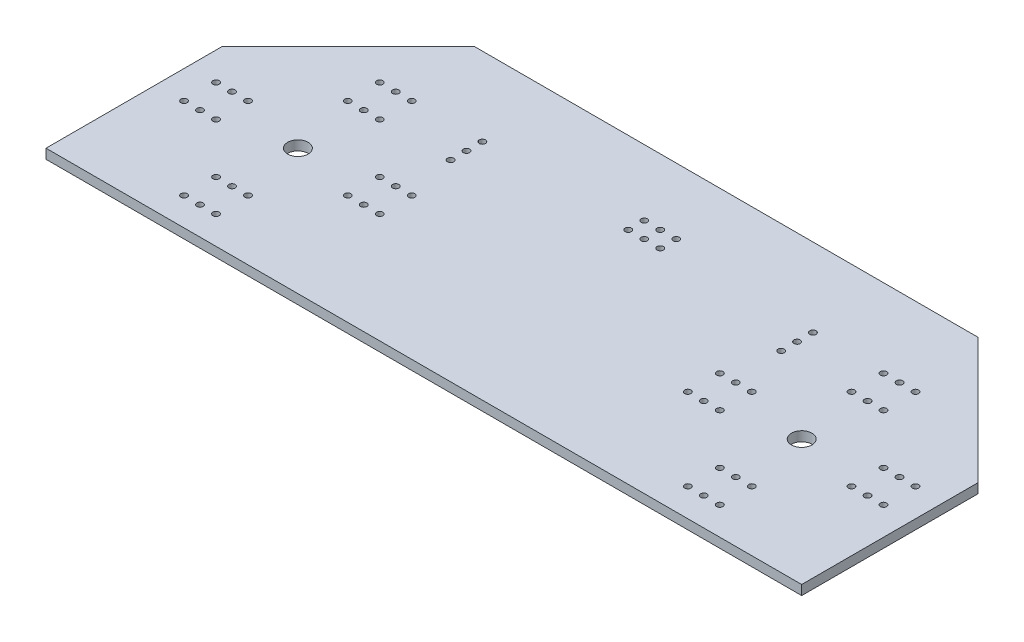
SolidWorks part; units mm, degrees
ref_plane "Front Plane" through (0, 0, 0) normal (0, 0, 1) x (1, 0, 0)
ref_plane "Top Plane" through (0, 0, 0) normal (0, 1, 0) x (1, 0, 0)
ref_plane "Right Plane" through (0, 0, 0) normal (1, 0, 0) x (0, 0, -1)
sketch "Sketch1" plane through (0, 0, 0) normal (0, 1, 0) x (1, 0, 0)
  line L0 (0, 0) -> (0, 13) construction
  line L1 (-60, -20) -> (60, -20)
  line L2 (-60, -20) -> (-60, 28)
  line L3 (-60, 28) -> (60, 28)
  line L4 (60, -20) -> (60, 28)
  line L5 (0, 0) -> (60, 28) construction
  line L6 (-60, 28) -> (0, 0) construction
  line L11 (0, 13) -> (0, 28) construction
  point P0 (0, 0)
  dimension "D1" = 120
  dimension "D2" = 28
  dimension "D6" = 20
extrude "Boss-Extrude1" add sketch "Sketch1" along normal blind 1.53
sketch "Sketch2" plane through (0, 1.53, 0) normal (0, 1, 0) x (1, 0, 0)
  line L0 (-55.54, 2.54) -> (-53, 2.54) construction
  line L1 (-53, 2.54) -> (-50.46, 2.54) construction
  line L2 (-53, 2.54) -> (-53, -2.54) construction
  line L3 (-53, -2.54) -> (-50.46, -2.54) construction
  line L4 (-53, -2.54) -> (-55.54, -2.54) construction
  line L5 (-53, 0) -> (-27, 0) construction
  line L6 (-29.54, 2.54) -> (-27, 2.54) construction
  line L7 (-27, 2.54) -> (-24.46, 2.54) construction
  line L8 (-27, 2.54) -> (-27, -2.54) construction
  line L9 (-27, -2.54) -> (-24.46, -2.54) construction
  line L10 (-27, -2.54) -> (-29.54, -2.54) construction
  line L11 (-42.54, 15.54) -> (-40, 15.54) construction
  line L12 (-40, 15.54) -> (-37.46, 15.54) construction
  line L13 (-40, 15.54) -> (-40, 10.46) construction
  line L14 (-40, 10.46) -> (-37.46, 10.46) construction
  line L15 (-40, 10.46) -> (-42.54, 10.46) construction
  line L16 (-42.54, -10.46) -> (-40, -10.46) construction
  line L17 (-40, -10.46) -> (-37.46, -10.46) construction
  line L18 (-40, -10.46) -> (-40, -15.54) construction
  line L19 (-40, -15.54) -> (-37.46, -15.54) construction
  line L20 (-40, -15.54) -> (-42.54, -15.54) construction
  line L21 (-40, -13) -> (-40, 0) construction
  line L22 (-40, 0) -> (-40, 13) construction
  line L23 (-27, 0) -> (0, 0) construction
  circle A0 centre (-55.54, 2.54) radius 0.5
  circle A1 centre (-53, 2.54) radius 0.5
  circle A2 centre (-50.46, 2.54) radius 0.5
  circle A3 centre (-55.54, -2.54) radius 0.5
  circle A4 centre (-53, -2.54) radius 0.5
  circle A5 centre (-50.46, -2.54) radius 0.5
  circle A6 centre (-29.54, 2.54) radius 0.5
  circle A7 centre (-27, 2.54) radius 0.5
  circle A8 centre (-24.46, 2.54) radius 0.5
  circle A9 centre (-29.54, -2.54) radius 0.5
  circle A10 centre (-27, -2.54) radius 0.5
  circle A11 centre (-24.46, -2.54) radius 0.5
  circle A12 centre (-42.54, 15.54) radius 0.5
  circle A13 centre (-40, 15.54) radius 0.5
  circle A14 centre (-37.46, 15.54) radius 0.5
  circle A15 centre (-42.54, 10.46) radius 0.5
  circle A16 centre (-40, 10.46) radius 0.5
  circle A17 centre (-37.46, 10.46) radius 0.5
  circle A18 centre (-42.54, -10.46) radius 0.5
  circle A19 centre (-40, -10.46) radius 0.5
  circle A20 centre (-37.46, -10.46) radius 0.5
  circle A21 centre (-42.54, -15.54) radius 0.5
  circle A22 centre (-40, -15.54) radius 0.5
  circle A23 centre (-37.46, -15.54) radius 0.5
  circle A24 centre (-40, 0) radius 1.625
  point P15 (-27, 0)
  dimension "D1" = 1
  dimension "D7" = 3.25
  dimension "D2" = 2.54
  dimension "D3" = 5.08
  dimension "D4" = 26
  dimension "D5" = 26
  dimension "D6" = 40
extrude "Cut-Extrude1" cut sketch "Sketch2" against normal through all
mirror "Mirror1" about plane through (0, 0, 0) normal (1, 0, 0) of "Cut-Extrude1"
sketch "Sketch5" plane through (0, 1.53, 0) normal (0, 1, 0) x (1, 0, 0)
  line L0 (-2.54, 17.54) -> (0, 17.54) construction
  line L1 (0, 17.54) -> (2.54, 17.54) construction
  line L2 (0, 17.54) -> (0, 15) construction
  line L3 (0, 15) -> (2.54, 15) construction
  line L4 (0, 15) -> (-2.54, 15) construction
  line L5 (0, 0) -> (0, 15) construction
  circle A0 centre (-2.54, 17.54) radius 0.5
  circle A1 centre (0, 17.54) radius 0.5
  circle A2 centre (2.54, 17.54) radius 0.5
  circle A3 centre (-2.54, 15) radius 0.5
  circle A4 centre (0, 15) radius 0.5
  circle A5 centre (2.54, 15) radius 0.5
  dimension "D1" = 2.54
  dimension "D2" = 2.54
  dimension "D3" = 15
extrude "Cut-Extrude2" cut sketch "Sketch5" against normal through all
sketch "Sketch6" plane through (0, 1.53, 0) normal (0, 1, 0) x (1, 0, 0)
  line L0 (-40, 28) -> (-60, 8)
  line L1 (60, 28) -> (-60, 28) construction
  line L2 (-60, 28) -> (-60, -20) construction
  line L12 (60, -20) -> (60, 28) construction
  line L13 (60, -14) -> (60, 8)
  line L14 (60, 8) -> (40, 28)
  line L16 (0, 0) -> (0, -18) construction
  line L17 (0, 0) -> (0, 28) construction
  line L18 (-60, 8) -> (-60, 28)
  line L23 (-60, 28) -> (-40, 28)
  line L24 (40, 28) -> (60, 28)
  line L25 (60, 28) -> (60, 8)
  dimension "D1" = 45
  dimension "D2" = 45
  dimension "D3" = 80
extrude "Cut-Extrude4" cut sketch "Sketch6" against normal through all contours L23 L18 L0 | L25 L24 L14 region at (-53.3333, 1.53, -21.3333) region at (53.3333, 1.53, -21.3333)
sketch "Sketch7" plane through (0, 1.53, 0) normal (0, 1, 0) x (1, 0, 0)
  line L0 (-26.25, 15.54) -> (-26.25, 13.02) construction
  line L1 (-26.25, 13.02) -> (-26.25, 10.5) construction
  line L2 (-26.25, 10.5) -> (-26.25, 0) construction
  line L3 (-26.25, 0) -> (0, 0) construction
  line L4 (0, 0.353) -> (0, 11.8498) construction
  line L5 (26.25, 13.02) -> (26.25, 10.5) construction
  line L6 (26.25, 15.54) -> (26.25, 13.02) construction
  circle A0 centre (-26.25, 15.54) radius 0.5
  circle A1 centre (-26.25, 13.02) radius 0.5
  circle A2 centre (-26.25, 10.5) radius 0.5
  circle A3 centre (26.25, 10.5) radius 0.5
  circle A4 centre (26.25, 13.02) radius 0.5
  circle A5 centre (26.25, 15.54) radius 0.5
  dimension "D1" = 1
  dimension "D2" = 5.04
  dimension "D3" = 26.25
  dimension "D4" = 10.5
extrude "Cut-Extrude5" cut sketch "Sketch7" against normal through all
